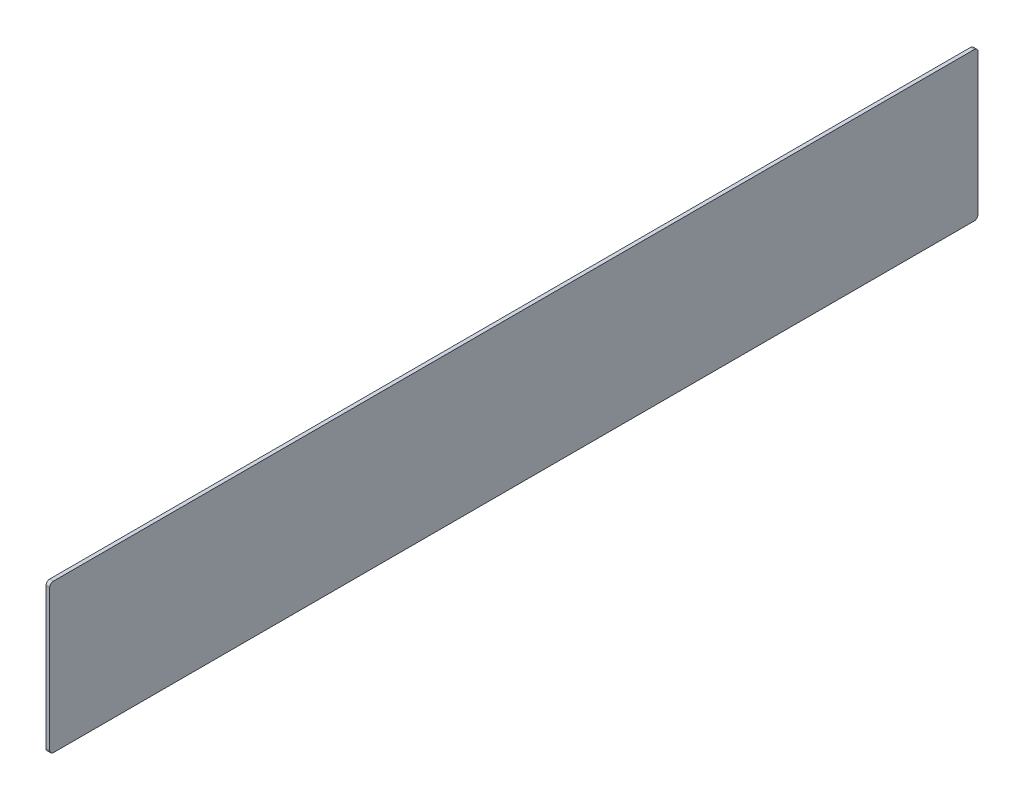
SolidWorks part; units mm, degrees
ref_plane "Front Plane" through (0, 0, 0) normal (0, 0, 1) x (1, 0, 0)
ref_plane "Top Plane" through (0, 0, 0) normal (0, 1, 0) x (1, 0, 0)
ref_plane "Right Plane" through (0, 0, 0) normal (1, 0, 0) x (0, 0, -1)
sketch "Sketch1" plane through (0, 0, 0) normal (1, 0, 0) x (0, 0, -1)
  line L1 (-269.9468, -60.2926) -> (230.0532, -60.2926)
  line L2 (-269.9468, -60.2926) -> (-269.9468, -140.2926)
  line L3 (-269.9468, -140.2926) -> (230.0532, -140.2926)
  line L4 (230.0532, -60.2926) -> (230.0532, -140.2926)
  dimension "D1" = 500
  dimension "D2" = 80
extrude "Boss-Extrude1" add sketch "Sketch1" along normal blind 2
fillet "Fillet1" radius 2 4 edges at (1, -140.2926, -230.0532) (1, -60.2926, -230.0532) (1, -140.2926, 269.9468) (1, -60.2926, 269.9468)
